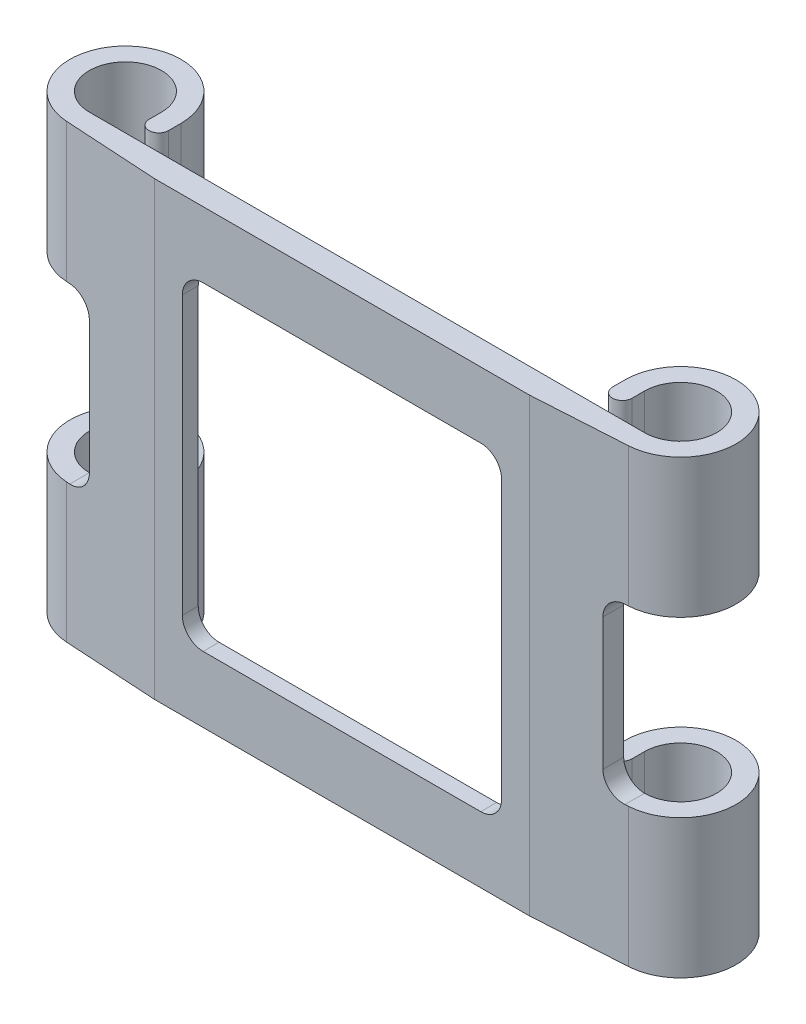
SolidWorks part; units mm, degrees
ref_plane "Front Plane" through (0, 0, 0) normal (0, 0, 1) x (1, 0, 0)
ref_plane "Top Plane" through (0, 0, 0) normal (0, 1, 0) x (1, 0, 0)
ref_plane "Right Plane" through (0, 0, 0) normal (1, 0, 0) x (0, 0, -1)
sketch "Sketch1" plane through (0, 0, 0) normal (0, 1, 0) x (1, 0, 0)
  line L1 (40, 3.6) -> (-40, 3.6)
  line L2 (32, 8.8) -> (34.8, 8.8) construction
  line L3 (32, 8.8) -> (32, 13.0144) construction
  line L4 (33.0122, 5.6) -> (37.2531, 5.6) construction
  line L5 (0, -1.941) -> (0, 24.0569) construction
  line L6 (32, 8.8) -> (32, 7)
  line L7 (34.8, 8.8) -> (34.8, 7)
  line L9 (-27, 0) -> (27, 0)
  line L10 (27, 0) -> (40.4825, 0.8146)
  line L11 (-27, 0) -> (-40.4825, 0.8146)
  line L12 (-34.8, 8.8) -> (-34.8, 7)
  line L13 (-32, 8.8) -> (-32, 7)
  arc A0 (40, 3.6) -> (34.8, 8.8) centre (40, 8.8) ccw
  arc A1 (40.4825, 0.8146) -> (32, 8.8) centre (40, 8.8) ccw
  arc A2 (32, 7) -> (34.8, 7) centre (33.4, 7) ccw
  arc A3 (-32, 7) -> (-34.8, 7) centre (-33.4, 7) cw
  arc A4 (-40.4825, 0.8146) -> (-32, 8.8) centre (-40, 8.8) cw
  arc A5 (-40, 3.6) -> (-34.8, 8.8) centre (-40, 8.8) cw
  point P18 (0, 0)
  point P19 (0, 0)
  point P20 (37.2531, 5.6)
  point P22 (33.0122, 5.6)
  point P28 (34, 11.0144)
  dimension "D3" = 2
  dimension "D4" = 8
  dimension "D1" = 2.8
  dimension "D2" = 80
  dimension "D5" = 3.6
  dimension "D6" = 54
extrude "Boss-Extrude1" add sketch "Sketch1" along normal blind 65
ref_plane "Plane1" through (0, 0, -3.6) normal (0, 0, -1) x (-1, 0, 0)
sketch "Sketch4" plane through (0, 0, 0) normal (1, 0, 0) x (0, 0, -1)
  line L0 (3.6, -35.75) -> (3.6, 35.75) construction
  line L6 (16.8, 45) -> (3.6, 45)
  line L7 (16.8, 45) -> (16.8, 20)
  line L8 (16.8, 20) -> (3.6, 20)
  line L9 (16.8, 0) -> (16.8, 65) construction
  line L10 (16.8, 32.5) -> (0, 32.5) construction
  line L11 (0, 65) -> (0, 0) construction
  line L12 (3.6, 45) -> (3.6, 20)
  line L13 (16.8, 45) -> (3.6, 20) construction
  line L14 (16.8, 20) -> (3.6, 45) construction
  point P0 (10.2, 32.5)
  dimension "D1" = 25
extrude "Cut-Extrude4" cut sketch "Sketch4" against normal through all both and the other way through all
sketch "Sketch5" plane through (0, 0, -3.6) normal (0, 0, -1) x (-1, 0, 0)
  line L0 (46.0795, 45) -> (40, 45)
  line L1 (46.0795, 45) -> (46.0795, 20)
  line L2 (37, 42) -> (37, 23)
  line L3 (46.0795, 32.5) -> (-46.0795, 32.5) construction
  line L4 (-46.0795, 20) -> (-46.0795, 45) construction
  line L5 (0, 65) -> (0, 0) construction
  line L6 (-40, 65) -> (40, 65) construction
  line L7 (-40, 0) -> (40, 0) construction
  line L8 (46.0795, 20) -> (40, 20)
  line L9 (-46.0795, 20) -> (-40, 20)
  line L10 (-37, 42) -> (-37, 23)
  line L11 (-46.0795, 45) -> (-46.0795, 20)
  line L12 (-46.0795, 45) -> (-40, 45)
  arc A0 (40, 45) -> (37, 42) centre (40, 42) ccw
  arc A1 (40, 20) -> (37, 23) centre (40, 23) cw
  arc A2 (-40, 20) -> (-37, 23) centre (-40, 23) ccw
  arc A3 (-40, 45) -> (-37, 42) centre (-40, 42) cw
  dimension "D1" = 3
extrude "Cut-Extrude5" cut sketch "Sketch5" against normal through all
sketch "Sketch2" plane through (0, 0, -3.6) normal (0, 0, -1) x (-1, 0, 0)
  line L0 (0, 14.2988) -> (0, -14.2988) construction
  line L1 (25.145, 7.355) -> (-25.145, 7.355)
  line L2 (25.145, 7.355) -> (25.145, 57.645)
  line L3 (25.145, 57.645) -> (-25.145, 57.645)
  line L4 (-25.145, 7.355) -> (-25.145, 57.645)
  line L5 (25.145, 7.355) -> (-25.145, 57.645) construction
  line L6 (25.145, 57.645) -> (-25.145, 7.355) construction
  line L7 (0, 0) -> (0, 65) construction
  line L8 (-40, 65) -> (40, 65) construction
  point P0 (0, 32.5)
  point P13 (0, 32.5)
  dimension "D1" = 50.29
extrude "Cut-Extrude1" cut sketch "Sketch2" against normal blind 1.31
sketch "Sketch3" plane through (0, 0, -2.29) normal (0, 0, -1) x (-1, 0, 0)
  line L1 (23, 9.5) -> (-23, 9.5)
  line L2 (23, 9.5) -> (23, 55.5)
  line L3 (23, 55.5) -> (-23, 55.5)
  line L4 (-23, 9.5) -> (-23, 55.5)
  line L5 (23, 9.5) -> (-23, 55.5) construction
  line L6 (23, 55.5) -> (-23, 9.5) construction
  point P0 (0, 32.5)
  dimension "D1" = 46
extrude "Cut-Extrude2" cut sketch "Sketch3" against normal through all
fillet "Fillet1" radius 3 4 edges at (-23, 55.5, -1.145) (23, 55.5, -1.145) (23, 9.5, -1.145) (-23, 9.5, -1.145)
